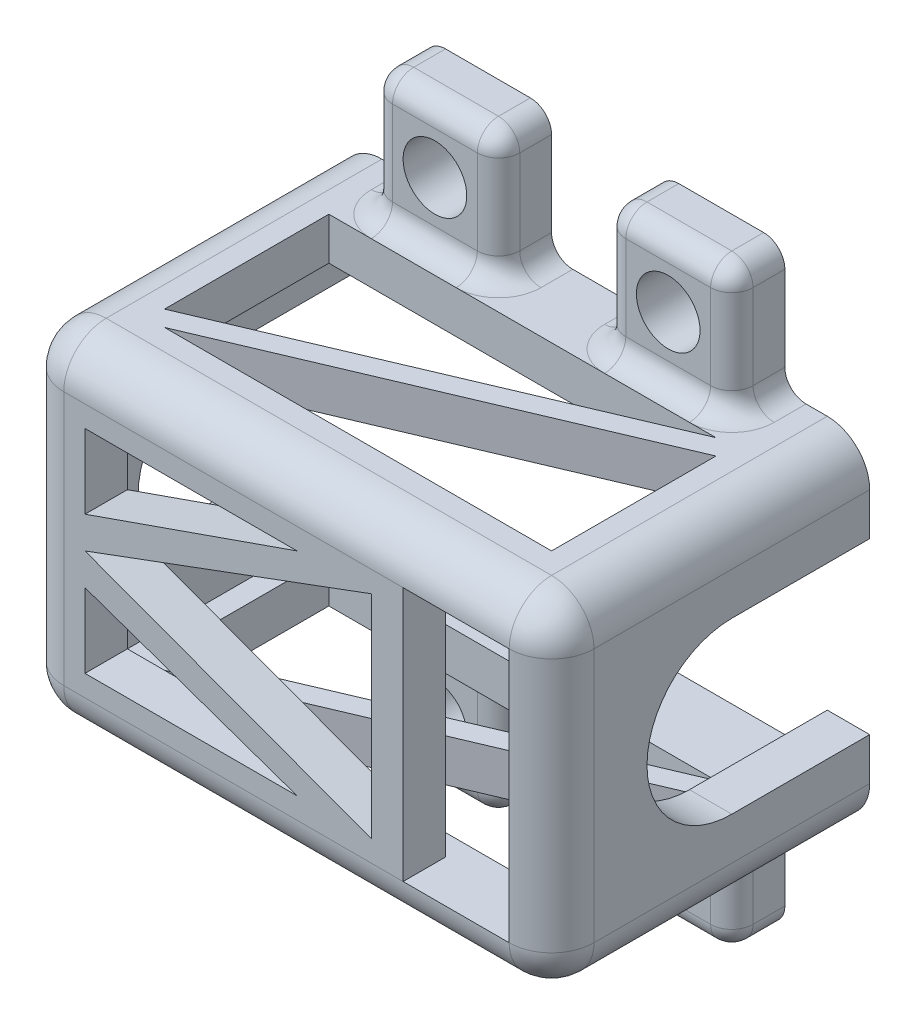
SolidWorks part; units mm, degrees
material "ABS"
ref_plane "Alzado" through (0, 0, 0) normal (0, 0, 1) x (1, 0, 0)
ref_plane "Planta" through (0, 0, 0) normal (0, 1, 0) x (1, 0, 0)
ref_plane "Vista lateral" through (0, 0, 0) normal (1, 0, 0) x (0, 0, -1)
sketch "Croquis1" plane through (0, 0, 0) normal (0, 0, 1) x (1, 0, 0)
  line L1 (0, 0) -> (23, 0)
  line L2 (0, 0) -> (0, 16)
  line L3 (0, 16) -> (23, 16)
  line L4 (23, 0) -> (23, 16)
  dimension "D1" = 16
  dimension "D2" = 23
extrude "Saliente-Extruir1" add sketch "Croquis1" along normal blind 15
sketch "Croquis2" plane through (23, 0, 0) normal (1, 0, 0) x (0, 0, -1)
  line L0 (0, 0) -> (0, 16) construction
  line L1 (-13, 2) -> (-2, 2)
  line L2 (-13, 2) -> (-13, 14)
  line L3 (-13, 14) -> (-2, 14)
  line L4 (-2, 2) -> (-2, 14)
  line L5 (-15, 0) -> (-15, 16) construction
  line L6 (-15, 16) -> (0, 16) construction
  line L7 (-15, 0) -> (0, 0) construction
  dimension "D1" = 2
  dimension "D2" = 2
  dimension "D3" = 2
  dimension "D4" = 2
extrude "Cortar-Extruir1" cut sketch "Croquis2" against normal blind 21
sketch "Croquis4" plane through (0, 0, 0) normal (-1, 0, 0) x (0, 0, 1)
  line L0 (0, 0) -> (15, 16) construction
  line L1 (15, 16) -> (15, 0) construction
  line L2 (15, 16) -> (0, 16) construction
  line L3 (7.5, 12) -> (0, 12)
  line L4 (0, 16) -> (0, 0) construction
  line L5 (0, 12) -> (0, 4)
  line L6 (0, 4) -> (7.5, 4)
  arc A1 (7.5, 12) -> (7.5, 4) centre (7.5, 8) cw
  dimension "D1" = 4
  dimension "D3" = 8
  dimension "D2" = 7.5
extrude "Cortar-Extruir2" cut sketch "Croquis4" against normal blind 23
sketch "Croquis5" plane through (0, 0, 15) normal (0, 0, 1) x (1, 0, 0)
  line L0 (23, 0) -> (23, 16) construction
  line L1 (23, 2) -> (18, 2)
  line L2 (23, 2) -> (23, 14)
  line L3 (23, 14) -> (18, 14)
  line L4 (18, 2) -> (18, 14)
  line L5 (23, 16) -> (0, 16) construction
  line L6 (0, 0) -> (23, 0) construction
  dimension "D1" = 2
  dimension "D2" = 2
  dimension "D3" = 5
extrude "Cortar-Extruir3" cut sketch "Croquis5" against normal blind 2
fillet "Redondeo1" radius 2 5 edges at (11.5, 16, 15) (11.5, 0, 15) (0, 16, 7.5) (0, 8, 15) (0, 0, 7.5)
sketch "Croquis8" plane through (0, 0, 15) normal (0, 0, 1) x (1, 0, 0)
  line L0 (16.5, 3) -> (16.5, 13)
  line L1 (18, 14) -> (18, 2) construction
  line L2 (16.5, 8) -> (3, 8) construction
  line L3 (3, 8) -> (16.5, 3)
  line L4 (3, 8) -> (16.5, 13)
  line L6 (3, 8) -> (3, 6.5005) construction
  line L7 (3, 6.5005) -> (3, 3)
  line L8 (3, 3) -> (13, 3)
  line L9 (13, 3) -> (3, 6.5005)
  line L10 (3, 8) -> (3, 9.5) construction
  line L11 (3, 9.5) -> (3, 13)
  line L12 (3, 13) -> (13, 13)
  line L13 (13, 13) -> (3, 9.5)
  line L14 (18, 14) -> (2, 14) construction
  line L15 (2, 2) -> (18, 2) construction
  line L19 (2, 14) -> (2, 2) construction
  dimension "D1" = 1.5
  dimension "D2" = 1
  dimension "D3" = 1.4995
  dimension "D4" = 1.5
  dimension "D5" = 1
  dimension "D6" = 1
  dimension "D7" = 5
  dimension "D8" = 5
extrude "Cortar-Extruir4" cut sketch "Croquis8" against normal through all
sketch "Croquis18" plane through (0, 0, 2) normal (0, 0, 1) x (1, 0, 0)
  line L1 (2, 14) -> (23, 14)
  line L2 (2, 14) -> (2, 2)
  line L3 (2, 2) -> (23, 2)
  line L4 (23, 14) -> (23, 2)
extrude "Cortar-Extruir8" cut sketch "Croquis18" against normal through all
sketch "Croquis17" plane through (23, 0, 0) normal (1, 0, 0) x (0, 0, -1)
  line L1 (0, 0) -> (-15, 0)
  line L2 (0, 0) -> (0, 16)
  line L3 (0, 16) -> (-15, 16)
  line L4 (-15, 0) -> (-15, 16)
  dimension "D1" = 15
extrude "Saliente-Extruir7" add sketch "Croquis17" along normal blind 2
fillet "Redondeo8" radius 2 3 edges at (25, 0, 7.5) (25, 16, 7.5) (25, 8, 15)
sketch "Croquis19" plane through (0, 16, 0) normal (0, 1, 0) x (1, 0, 0)
  line L0 (23, 0) -> (2, 0) construction
  line L1 (21, 0) -> (15, 0)
  line L2 (21, 0) -> (21, -2.5)
  line L3 (21, -2.5) -> (15, -2.5)
  line L4 (15, 0) -> (15, -2.5)
  line L5 (23, -13) -> (23, 0) construction
  line L6 (4, 0) -> (10, 0)
  line L7 (4, 0) -> (4, -2.5)
  line L8 (4, -2.5) -> (10, -2.5)
  line L9 (10, 0) -> (10, -2.5)
  line L10 (2, 0) -> (2, -13) construction
  dimension "D1" = 2
  dimension "D2" = 2
  dimension "D3" = 2.5
  dimension "D4" = 2.5
  dimension "D5" = 6
  dimension "D6" = 6
extrude "Saliente-Extruir8" add sketch "Croquis19" along normal blind 6
sketch "Croquis20" plane through (0, 0, 0) normal (0, -1, 0) x (1, 0, 0)
  line L0 (2, 0) -> (23, 0) construction
  line L1 (4, 0) -> (10, 0)
  line L2 (4, 0) -> (4, 2.5)
  line L3 (4, 2.5) -> (10, 2.5)
  line L4 (10, 0) -> (10, 2.5)
  line L5 (2, 13) -> (2, 0) construction
  line L6 (21, 0) -> (15, 0)
  line L7 (21, 0) -> (21, 2.5)
  line L8 (21, 2.5) -> (15, 2.5)
  line L9 (15, 0) -> (15, 2.5)
  line L10 (23, 0) -> (23, 13) construction
  dimension "D1" = 2
  dimension "D2" = 2
  dimension "D3" = 2.5
  dimension "D4" = 2.5
  dimension "D5" = 6
  dimension "D6" = 6
extrude "Saliente-Extruir9" add sketch "Croquis20" along normal blind 6
sketch "Croquis21" plane through (0, 0, 2.5) normal (0, 0, 1) x (1, 0, 0)
  line L0 (4, 22) -> (10, 16) construction
  line L1 (15, 22) -> (21, 16) construction
  line L3 (21, 0) -> (15, -6) construction
  line L5 (10, 0) -> (4, -6) construction
  circle A0 centre (18, 19) radius 1.5
  circle A1 centre (7, 19) radius 1.5
  circle A2 centre (7, -3) radius 1.5
  circle A3 centre (18, -3) radius 1.5
  dimension "D1" = 3
  dimension "D2" = 3
  dimension "D3" = 3
  dimension "D4" = 3
extrude "Cortar-Extruir9" cut sketch "Croquis21" against normal through all
fillet "Redondeo9" radius 1 32 edges at (15, 0, 1.25) (21, 0, 1.25) (10, 0, 1.25) (4, 0, 1.25) (21, 16, 1.25) (15, 16, 1.25) (4, 16, 1.25) (10, 16, 1.25) (21, -6, 1.25) (15, -6, 1.25) (18, -6, 2.5) (15, -3, 2.5) (21, -3, 2.5) (18, 0, 2.5) (7, 0, 2.5) (10, -6, 1.25) (4, -6, 1.25) (4, -3, 2.5) (10, -3, 2.5) (7, -6, 2.5) (21, 22, 1.25) (15, 22, 1.25) (21, 19, 2.5) (18, 22, 2.5) (15, 19, 2.5) (18, 16, 2.5) (10, 22, 1.25) (4, 22, 1.25) (7, 16, 2.5) (4, 19, 2.5) (10, 19, 2.5) (7, 22, 2.5)
sketch "Croquis22" plane through (0, 0, 0) normal (0, -1, 0) x (1, 0, 0)
  line L1 (3, 3.5) -> (22, 3.5) construction
  line L6 (22, 3.5) -> (21.25, 3.5) construction
  line L9 (3, 4.25) -> (3, 3.5) construction
  line L10 (3, 3.5) -> (3.75, 3.5) construction
  line L12 (3, 11.25) -> (21.25, 3.5)
  line L13 (22, 11.25) -> (22, 12) construction
  line L14 (22, 12) -> (21.25, 12) construction
  line L15 (21.25, 3.5) -> (3, 3.5)
  line L16 (3, 3.5) -> (3, 11.25)
  line L17 (22, 4.25) -> (3.75, 12)
  line L18 (3.75, 12) -> (22, 12)
  line L19 (22, 12) -> (22, 4.25)
  line L20 (2, 13) -> (2, 0) construction
  line L21 (23, 0) -> (23, 13) construction
  line L22 (23, 13) -> (2, 13) construction
  line L23 (11, 0) -> (14, 0) construction
  dimension "D1" = 1.75
  dimension "D2" = 1.75
  dimension "D3" = 1
  dimension "D4" = 3.5
  dimension "D5" = 1
  dimension "D6" = 1
  dimension "D7" = 0.9835
extrude "Cortar-Extruir10" cut sketch "Croquis22" against normal blind 16
sketch "Croquis23" plane through (25, 0, 0) normal (1, 0, 0) x (0, 0, -1)
  line L0 (0, 8) -> (-6.5, 8) construction
  line L1 (0, 2) -> (0, 14) construction
  line L2 (-6.5, 8) -> (-6.5, 2) construction
  line L3 (-13, 2) -> (0, 2) construction
  line L4 (0, 8) -> (0, 4) construction
  line L5 (0, 4) -> (0, 12)
  line L6 (0, 12) -> (-6.5, 12)
  line L7 (0, 4) -> (-6.5, 4)
  arc A0 (-6.5, 4) -> (-6.5, 12) centre (-6.5, 8) cw
  dimension "D1" = 4
  dimension "D2" = 2
extrude "Cortar-Extruir11" cut sketch "Croquis23" against normal blind 2
